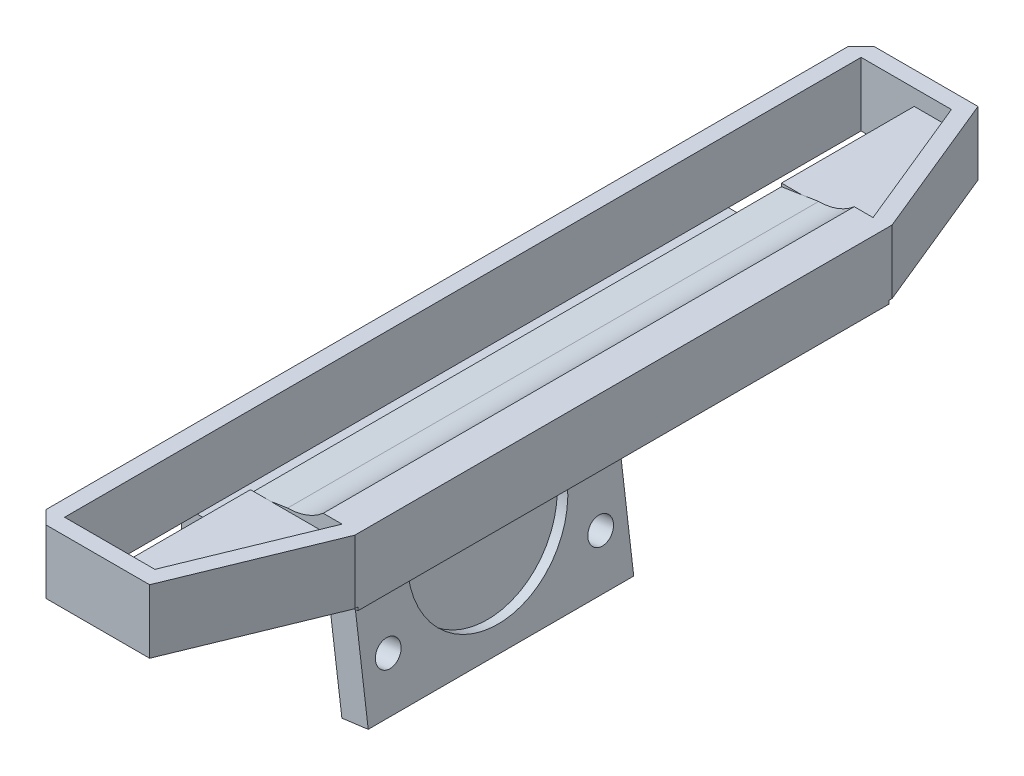
SolidWorks part; units mm, degrees
ref_plane "Ebene vorne" through (0, 0, 0) normal (0, 0, 1) x (1, 0, 0)
ref_plane "Ebene oben" through (0, 0, 0) normal (0, 1, 0) x (1, 0, 0)
ref_plane "Ebene rechts" through (0, 0, 0) normal (1, 0, 0) x (0, 0, -1)
sketch "Skizze1" plane through (0, 0, 0) normal (0, 0, 1) x (1, 0, 0)
  line L1 (20, -15) -> (-20, -15)
  line L2 (20, -15) -> (20, 15)
  line L3 (20, 15) -> (-20, 15)
  line L4 (-20, -15) -> (-20, 15)
  line L5 (20, -15) -> (-20, 15) construction
  line L6 (20, 15) -> (-20, -15) construction
  point P0 (0, 0)
  point P6 (-20, 0)
  point P7 (20, 0)
  dimension "D1" = 30
  dimension "D2" = 40
extrude "Aufsatz-Linear austragen1" add sketch "Skizze1" along normal blind 160
sketch "Skizze2" plane through (0, 15, 0) normal (0, 1, 0) x (1, 0, 0)
  line L0 (-20, -160) -> (-20, 0) construction
  line L1 (-15, -5) -> (-5, -5)
  line L2 (-15, -5) -> (-15, -155)
  line L3 (-15, -155) -> (-5, -155)
  line L4 (-5, -5) -> (-5, -155)
  line L5 (20, -160) -> (-20, -160) construction
  dimension "D1" = 5
  dimension "D2" = 150
  dimension "D3" = 10
  dimension "D4" = 5
extrude "Schnitt-Linear austragen1" cut sketch "Skizze2" against normal through all
sketch "Skizze3" plane through (0, 0, 160) normal (0, 0, 1) x (1, 0, 0)
  line L0 (20, 15) -> (-20, 15) construction
  line L1 (-20, 15) -> (-20, -15) construction
  line L2 (-5, -15) -> (-5, -6.6)
  line L3 (-20, -15) -> (20, -15) construction
  line L4 (-5, -15) -> (-15, -15)
  line L5 (-15, -15) -> (-15, 15)
  line L6 (-15, 15) -> (-3, 15)
  line L7 (-5, -6.6) -> (2, -5.5)
  line L8 (12.25, 4.75) -> (12.25, 15)
  line L9 (12.25, 15) -> (-3, 15)
  arc A0 (2, -5.5) -> (12.25, 4.75) centre (2, 4.75) ccw
  dimension "D1" = 10.25
  dimension "D2" = 17
  dimension "D3" = 8.4
  dimension "D4" = 5
  dimension "D5" = 10
  dimension "D6" = 10.25
extrude "Schnitt-Linear austragen2" cut sketch "Skizze3" against normal offset from surface (100 mm away) 30 from offset 30 up to face at (0, 0, 0) offset against normal yes
sketch "Skizze4" plane through (0, 15, 0) normal (0, 1, 0) x (1, 0, 0)
  line L0 (12.25, -30) -> (12.25, -130) construction
  line L1 (20, -104.5) -> (12.25, -104.5)
  line L2 (20, -104.5) -> (20, -55.5)
  line L3 (20, -55.5) -> (12.25, -55.5)
  line L4 (12.25, -104.5) -> (12.25, -55.5)
  line L5 (20, -104.5) -> (12.25, -55.5) construction
  line L6 (20, -55.5) -> (12.25, -104.5) construction
  line L7 (20, 0) -> (-20, 0) construction
  line L8 (20, -160) -> (20, 0) construction
  point P0 (16.125, -80)
  dimension "D1" = 80
  dimension "D2" = 49
  dimension "D3" = 0
extrude "Schnitt-Linear austragen3" cut sketch "Skizze4" against normal blind 15.6
sketch "Skizze5" plane through (12.25, 0, 0) normal (1, 0, 0) x (0, 0, -1)
  line L1 (-104.5, 4.75) -> (-55.5, 4.75)
  line L2 (-104.5, 4.75) -> (-104.5, -0.6)
  line L3 (-104.5, -0.6) -> (-55.5, -0.6)
  line L4 (-55.5, 4.75) -> (-55.5, -0.6)
extrude "Schnitt-Linear austragen4" cut sketch "Skizze5" against normal blind 5
sketch "Skizze6" plane through (0, 15, 0) normal (0, 1, 0) x (1, 0, 0)
  line L0 (-5, -5) -> (2, -5)
  line L1 (2, -5) -> (12.25, -30)
  line L2 (12.25, -30) -> (-5, -30)
  line L3 (-5, -30) -> (-5, -5)
  dimension "D1" = 17
extrude "Schnitt-Linear austragen5" cut sketch "Skizze6" against normal blind 21
ref_plane "Ebene1" through (0, 0, 80) normal (0, 0, 1) x (1, 0, 0)
mirror "Spiegeln3" about plane through (0, 0, 80) normal (0, 0, 1) of "Schnitt-Linear austragen5"
sketch "Skizze7" plane through (-20, 0, 0) normal (-1, 0, 0) x (0, 0, 1)
  line L0 (56, 5) -> (104, 5) construction
  line L1 (56, 13) -> (104, 13)
  line L2 (56, -3) -> (104, -3)
  line L3 (0, 15) -> (0, -15) construction
  line L4 (160, 15) -> (0, 15) construction
  arc A0 (56, 13) -> (56, -3) centre (56, 5) ccw
  arc A1 (104, -3) -> (104, 13) centre (104, 5) ccw
  point P2 (80, 5)
  dimension "D2" = 8
  dimension "D1" = 48
  dimension "D3" = 80
  dimension "D4" = 10
extrude "Schnitt-Linear austragen6" cut sketch "Skizze7" against normal blind 5
sketch "Sketch1" plane through (0, 0, 160) normal (0, 0, 1) x (1, 0, 0)
  line L0 (-20, -15) -> (-20, -20.2661)
  line L1 (-20, -20.2661) -> (20, -15)
  line L2 (20, -15) -> (-20, -15)
  dimension "D1" = 7.5
extrude "Boss-Extrude1" add sketch "Sketch1" against normal blind 100 from offset 30 offset against normal yes
sketch "Sketch7" plane through (0, 15, 0) normal (0, 1, 0) x (1, 0, 0)
  line L0 (5.3539, 0) -> (20, -35.7221)
  line L1 (20, 0) -> (-20, 0) construction
  line L2 (20, -55.5) -> (20, 0) construction
  line L3 (20, -35.7221) -> (45.1921, 3.8342)
  line L4 (45.1921, 3.8342) -> (5.3539, 0)
  line L5 (12.25, -30) -> (2, -5) construction
  line L6 (12.25, -30) -> (2, -5) construction
  dimension "D1" = 5
extrude "Cut-Extrude1" cut sketch "Sketch7" against normal through all
sketch "Sketch10" plane through (0, -3, 0) normal (0, 1, 0) x (1, 0, 0)
  line L1 (-41.0332, 19.8386) -> (39.9405, 19.8386)
  line L2 (-41.0332, 19.8386) -> (-41.0332, -175.5724)
  line L3 (-41.0332, -175.5724) -> (39.9405, -175.5724)
  line L4 (39.9405, 19.8386) -> (39.9405, -175.5724)
  line L7 (12.25, -130) -> (2, -155) construction
  line L8 (12.25, -30) -> (2, -5) construction
  line L9 (2, -5) -> (-15, -5) construction
  line L11 (-15, -155) -> (2, -155) construction
  line L12 (-15, -5) -> (-15, -155) construction
  line L14 (12.25, -30) -> (12.25, -55.5) construction
  line L25 (4.0124, -2) -> (15.25, -29.4089)
  line L30 (-18, -158) -> (4.0124, -158)
  line L31 (4.0124, -2) -> (-18, -2)
  line L32 (-18, -2) -> (-18, -158)
  line L33 (15.25, -29.4089) -> (15.25, -130.5911)
  line L34 (12.25, -30) -> (2, -5) construction
  line L35 (4.0124, -158) -> (15.25, -130.5911)
  line L36 (12.25, -130) -> (2, -155) construction
  point P23 (-6.9938, -2)
  dimension "D2" = 3
  dimension "D3" = 3
  dimension "D4" = 3
  dimension "D5" = 3
  dimension "D6" = 3
  dimension "D1" = 3
extrude "Cut-Extrude4" cut sketch "Sketch10" against normal blind 40
sketch "Sketch2" plane through (0, 0, 160) normal (0, 0, 1) x (1, 0, 0)
  line L0 (-18, -20.0028) -> (-12.779, -59.6606)
  line L1 (-12.779, -59.6606) -> (-7.8217, -59.008)
  line L2 (-7.8217, -59.008) -> (-13.0428, -19.3502)
  line L3 (-18, -20.0028) -> (15.25, -15.6253) construction
  line L4 (-13.0428, -19.3502) -> (-18, -20.0028)
  point P3 (0, 0)
  dimension "D1" = 5
  dimension "D2" = 40
extrude "Boss-Extrude2" add sketch "Sketch2" against normal blind 50 from offset 55 offset against normal yes
sketch "Sketch4" plane through (-20.2819, -2.6702, 0) normal (-0.9914, -0.1305, 0) x (0, 0, 1)
  line L1 (60, -28.0822) -> (100, -28.0822)
  line L2 (60, -28.0822) -> (60, -48.0822)
  line L3 (60, -48.0822) -> (100, -48.0822)
  line L4 (100, -28.0822) -> (100, -48.0822)
  line L5 (55, -17.4822) -> (55, -57.4822) construction
  line L6 (55, -17.4822) -> (30, -17.4822) construction
  point P10 (41.769, -22.1457)
  point P11 (43.5761, -17.4822)
  dimension "D1" = 40
  dimension "D2" = 20
  dimension "D3" = 30.6
  dimension "D4" = 5
hole_wizard "M4 Clearance Hole1" positions "Sketch5" profile "Sketch6" hole size "M4" standard "DIN" end condition through all
sketch "Sketch5" plane through (-20.2819, -2.6702, 0) normal (-0.9914, -0.1305, 0) x (0, 0, 1)
  point P0 (60, -28.0822)
  point P3 (100, -28.0822)
  point P6 (100, -48.0822)
  point P9 (60, -48.0822)
sketch "Sketch6" plane through (-16.6164, -30.5121, 60) normal (0, 0, 1) x (0.1305, -0.9914, 0)
  line L0 (0, 0) -> (0, 42.2437)
  line L1 (0, 42.2437) -> (2.4, 42.2437)
  line L2 (2.4, 42.2437) -> (2.4, 0)
  line L5 (2.4, 0) -> (0, 0)
  line L11 (0, -6.35) -> (0, 107.95) construction
  dimension "Thru Hole Dia." = 4.8
  dimension "Thru Hole Depth" = 42.2437
mirror "Mirror1" about plane through (0, 0, 80) normal (0, 0, 1) of "Cut-Extrude1"
sketch "Sketch8" plane through (-15.3247, -2.0175, 0) normal (0.9914, 0.1305, 0) x (0, 0, -1)
  circle A0 centre (-80, -38.0822) radius 15
  circle A1 centre (-100, -28.0822) radius 2.4 construction
  circle A2 centre (-100, -48.0822) radius 2.4 construction
  dimension "D1" = 30
  dimension "D2" = 20
  dimension "D3" = 10
extrude "Cut-Extrude2" cut sketch "Sketch8" against normal blind 2
chamfer "Chamfer1" distance 0.5 angle 45 16 edges at (-7.323, 15, 160) (-20, 15, 80) (-7.323, 15, 0) (12.677, 15, 17.8611) (20, 15, 45.6111) (16.125, 15, 55.5) (12.25, 15, 42.75) (7.125, 15, 17.5) (-6.5, 15, 5) (-15, 15, 80) (-6.5, 15, 155) (7.125, 15, 142.5) (12.25, 15, 117.25) (16.125, 15, 104.5) (20, 15, 114.3889) (12.677, 15, 142.1389)
sketch "Sketch9" plane through (0, 15, 0) normal (0, 1, 0) x (1, 0, 0)
  line L1 (-28.3576, 4.9021) -> (32.7992, 4.9021)
  line L2 (-28.3576, 4.9021) -> (-28.3576, -169.002)
  line L3 (-28.3576, -169.002) -> (32.7992, -169.002)
  line L4 (32.7992, 4.9021) -> (32.7992, -169.002)
extrude "Cut-Extrude3" cut sketch "Sketch9" against normal up to surface (18 mm away) up to face at (-16.5, -3, 80)
chamfer "Chamfer2" distance 2.5 angle 45 2 edges at (-18, -9, 158) (-18, -9, 2)
sketch "Sketch11" plane through (-18, 0, 0) normal (-1, 0, 0) x (0, 0, 1)
  line L0 (35, -16.5) -> (125, -16.5)
  line L4 (4.5, -3) -> (155.5, -3) construction
  point P2 (80, -3)
  dimension "D1" = 13.5
  dimension "D2" = 90
  dimension "D3" = 45
sketch "Sketch12" plane through (-18, 0, 0) normal (-1, 0, 0) x (0, 0, 1)
  text T0 "<b>Carologistics</b>" font "Century Gothic" height 10
extrude "Cut-Extrude5" cut sketch "Sketch12" against normal blind 1
